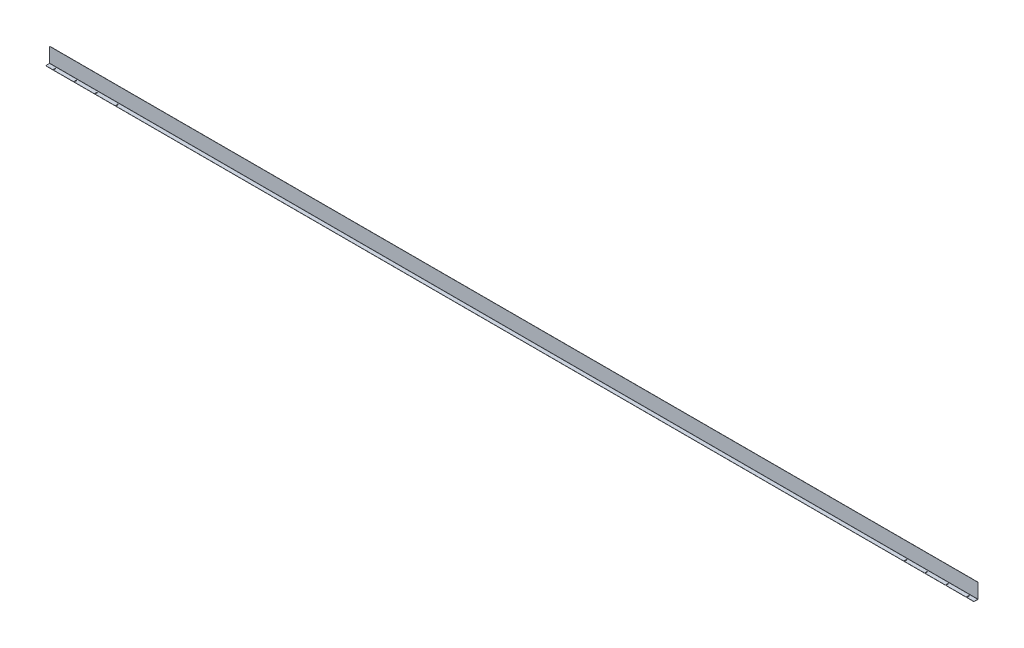
SolidWorks part; units mm, degrees
note: The reader was unsure of these and kept them because the rebuilt part matched: bend radius of "BaseBend4".
material "AISI 304"
ref_plane "Front Plane" through (0, 0, 0) normal (0, 0, 1) x (1, 0, 0)
ref_plane "Top Plane" through (0, 0, 0) normal (0, 1, 0) x (1, 0, 0)
ref_plane "Right Plane" through (0, 0, 0) normal (1, 0, 0) x (0, 0, -1)
sketch "Sketch1" plane through (0, 0, 0) normal (1, 0, 0) x (0, 0, -1)
  line L0 (0, 0) -> (0, 150)
  line L4 (0, 0) -> (-40, 0)
  dimension "D1" = 150
  dimension "D5" = 40
base flange "Base-Flange1" sketch "Sketch1" end condition mid plane depth 9472 reverse direction no thickness 2 reverse thickness direction no bend radius 1.3
bend "BaseBend4" bend radius 1.3 bend angle 90 parameters "D5"=7
fillet "Fillet1" radius 5 4 edges at (4736, 150, -1) (4736, -1, 40) (-4736, -1, 40) (-4736, 150, -1)
sketch "Sketch2" plane through (0, 0, 0) normal (0, 1, 0) x (1, 0, 0)
  line L0 (4731, 2) -> (-4731, 2) construction
  line L2 (-4657.5, -48) -> (-4664.5, -48)
  line L3 (-4736, -35) -> (-4736, -1.3) construction
  line L6 (-4657.5, -48) -> (-4657.5, -13)
  line L21 (-4657.5, -13) -> (-4664.5, -13)
  line L22 (-4664.5, -48) -> (-4664.5, -13)
  line L23 (-4657.5, -48) -> (-4664.5, -13) construction
  line L24 (-4657.5, -13) -> (-4664.5, -48) construction
  point P4 (0, 0)
  point P5 (0, 0)
  point P6 (0, 0)
  point P41 (-4661, -30.5)
  dimension "D1" = 15
  dimension "D2" = 75
  dimension "D7" = 7
  dimension "D8" = 35
extrude "Cut-Extrude1" cut sketch "Sketch2" against normal blind 10
pattern_linear "阵列(线性)1" count 4 spacing 212.51 along (1, 0, 0) of "Cut-Extrude1"
ref_plane "基准面1" through (0, 0, 0) normal (-1, 0, 0) x (0, 0, 1)
mirror "镜向1" about plane through (0, 0, 0) normal (-1, 0, 0) of "阵列(线性)1", "Cut-Extrude1"
sketch "Bend-Lines1" [suppressed] plane through (0, 0, 0) normal (0, 1, 0) x (1, 0, 0)
sketch "Bounding-Box1" [suppressed] plane through (0, 0, 0) normal (0, 1, 0) x (1, 0, 0)
sheet metal parameters "Sheet-Metal1" thickness 2 parameters "D1"=2
flat pattern "Flat-Pattern1" [suppressed]
sketch "Bend-Lines2" plane through (0, 0, 0) normal (0, 0, 1) x (1, 0, 0)
  line L6 (500, -0.3423) -> (-500, -0.3423) construction
  line L7 (500, -0.3423) -> (-500, -0.3423) construction
sketch3d "Bounding-Box2" [suppressed]
  line L0 (-1000, 25.0001, 0) -> (0, 25, 0) construction
  line L1 (-1000, -43.6845, 0) -> (0, -43.6845, 0) construction
  line L2 (-1000, 25.0001, 0) -> (-1000, -43.6845, 0) construction
  line L3 (0, 25, 0) -> (0, -43.6845, 0) construction
bend of the flat pattern "Flatten-<BaseBend4>1"
sheet metal parameters "Sheet-Metal2" thickness 2 parameters "D1"=2
flat pattern "Flat-Pattern1"
sketch "Bend-Lines2" plane through (0, 0, 0) normal (0, 0, 1) x (1, 0, 0)
  line L6 (2373.5, -0.3423) -> (-2373.5, -0.3423) construction
  line L7 (2373.5, -0.3423) -> (-2373.5, -0.3423) construction
sketch3d "Bounding-Box2" [suppressed]
  line L0 (-4747, 150.0004, 0) -> (0, 150, 0) construction
  line L1 (-4747, -40.6842, 0) -> (0, -40.6845, 0) construction
  line L2 (-4747, 150.0004, 0) -> (-4747, -40.6842, 0) construction
  line L3 (0, 150, 0) -> (0, -40.6845, 0) construction
bend of the flat pattern "Flatten-<BaseBend4>1"
sheet metal parameters "钣金3" thickness 2 parameters "D1"=2
flat pattern "Flat-Pattern1"
sketch "Bend-Lines2" plane through (0, 0, 0) normal (0, 0, 1) x (1, 0, 0)
  line L6 (4746.75, -0.3423) -> (-4746.75, -0.3423) construction
  line L7 (4746.75, -0.3423) -> (-4746.75, -0.3423) construction
sketch3d "Bounding-Box2" [suppressed]
  line L0 (-9493.5, 150.0007, 0) -> (0, 150, 0) construction
  line L1 (-9493.5, -40.6838, 0) -> (0, -40.6845, 0) construction
  line L2 (-9493.5, 150.0007, 0) -> (-9493.5, -40.6838, 0) construction
  line L3 (0, 150, 0) -> (0, -40.6845, 0) construction
bend of the flat pattern "Flatten-<BaseBend4>1"
sheet metal parameters "钣金4" thickness 2 parameters "D1"=2
flat pattern "Flat-Pattern1"
sketch "Bend-Lines2" plane through (0, 0, 0) normal (0, 0, 1) x (1, 0, 0)
  line L6 (4736, -0.3423) -> (-4736, -0.3423) construction
  line L7 (4736, -0.3423) -> (-4736, -0.3423) construction
sketch3d "Bounding-Box2" [suppressed]
  line L0 (-9472, 150.0007, 0) -> (0, 150, 0) construction
  line L1 (-9472, -40.6838, 0) -> (0, -40.6845, 0) construction
  line L2 (-9472, 150.0007, 0) -> (-9472, -40.6838, 0) construction
  line L3 (0, 150, 0) -> (0, -40.6845, 0) construction
bend of the flat pattern "Flatten-<BaseBend4>1"
